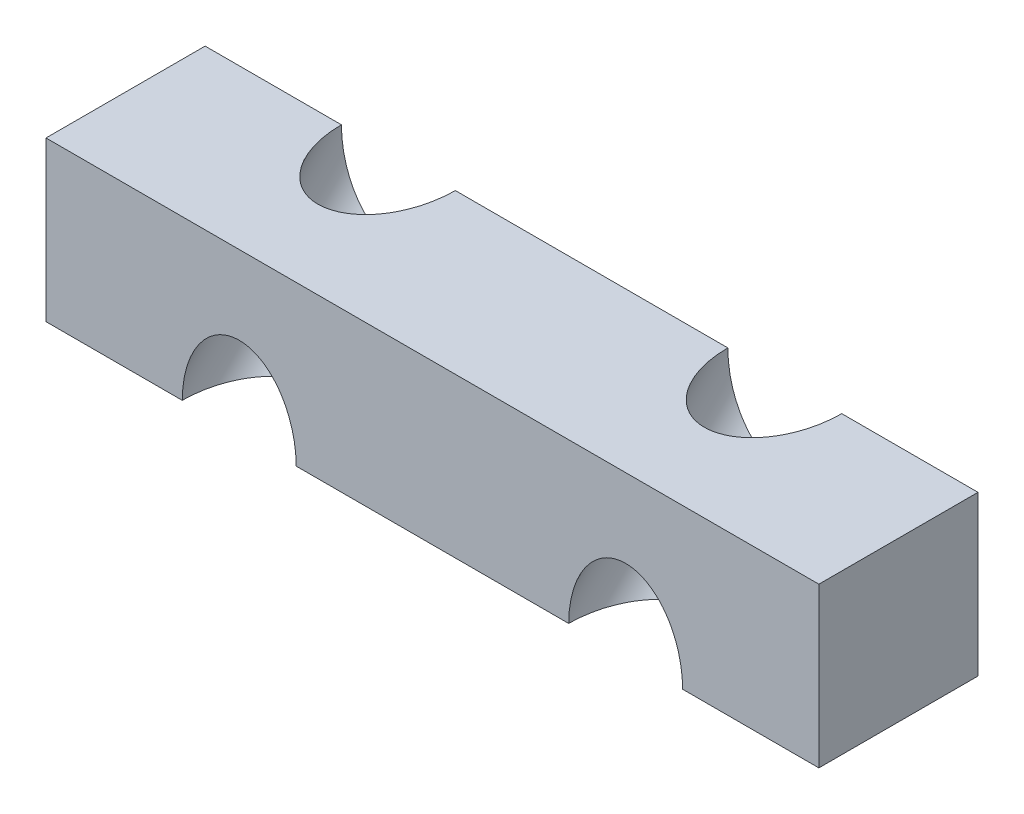
SolidWorks part; units mm, degrees
ref_plane "Front Plane" through (0, 0, 0) normal (0, 0, 1) x (1, 0, 0)
ref_plane "Top Plane" through (0, 0, 0) normal (0, 1, 0) x (1, 0, 0)
ref_plane "Right Plane" through (0, 0, 0) normal (1, 0, 0) x (0, 0, -1)
other "Configuration Table"
sketch "sketch1" plane through (0, 0, 0) normal (0, 1, 0) x (1, 0, 0)
  line L1 (0, 0) -> (34, 0)
  line L2 (0, 0) -> (0, -7)
  line L3 (0, -7) -> (34, -7)
  line L4 (34, 0) -> (34, -7)
  dimension "D1" = 7
  dimension "D2" = 34
extrude "Boss-Extrude1" add sketch "sketch1" along normal blind 7
ref_plane "Plane1" through (0, 0, 0) normal (0, 0.7071, -0.7071) x (-1, 0, 0)
sketch "Sketch6" plane through (0, 0, 0) normal (0, 0.7071, -0.7071) x (-1, 0, 0)
  line L0 (-34, 4.9497) -> (-25.5, 4.9497) construction
  line L1 (0, 0) -> (-34, 0)
  line L2 (0, 0) -> (0, 9.8995)
  line L3 (0, 9.8995) -> (-34, 9.8995)
  line L12 (-34, 0) -> (-34, 9.8995)
  line L13 (-25.5, 4.9497) -> (-8.5, 4.9497) construction
  circle A2 centre (-25.5, 4.9497) radius 2.505
  circle A3 centre (-8.5, 4.9497) radius 2.505
  dimension "D4" = 5.01
  dimension "D1" = 34
  dimension "D2" = 9.8995
  dimension "D3" = 8.5
  dimension "D6" = 17
  dimension "D5" = 2
extrude "Cut-Extrude2" cut sketch "Sketch6" against normal through all both and the other way through all flip side to cut
equation "\"D2@sketch1\" = \"length\""
equation "\"holes\" = 2"
equation "\"cdist\"= 17mm'centre distance between holes"
equation "\"width\"= 7mm"
equation "\"length\"= \"cdist\" * \"holes\""
equation "\"D1@sketch1\" = \"width\""
equation "\"hdiam\"= 5.01mm'Hole diametre"
equation "\"D4@Sketch6\"=\"hdiam\""
equation "\"D1@Boss-Extrude1\"=\"width\""
equation "\"tolerance\"= 0.04mm"
equation "\"D1@Sketch6\"=\"length\""
equation "\"D2@Sketch6\"=sqr(\"width\"^2 + \"width\"^2)"
equation "\"D3@Sketch6\"=\"cdist\"/2"
equation "\"D5@Sketch6\"=\"holes\""
equation "\"D6@Sketch6\"=\"cdist\""
